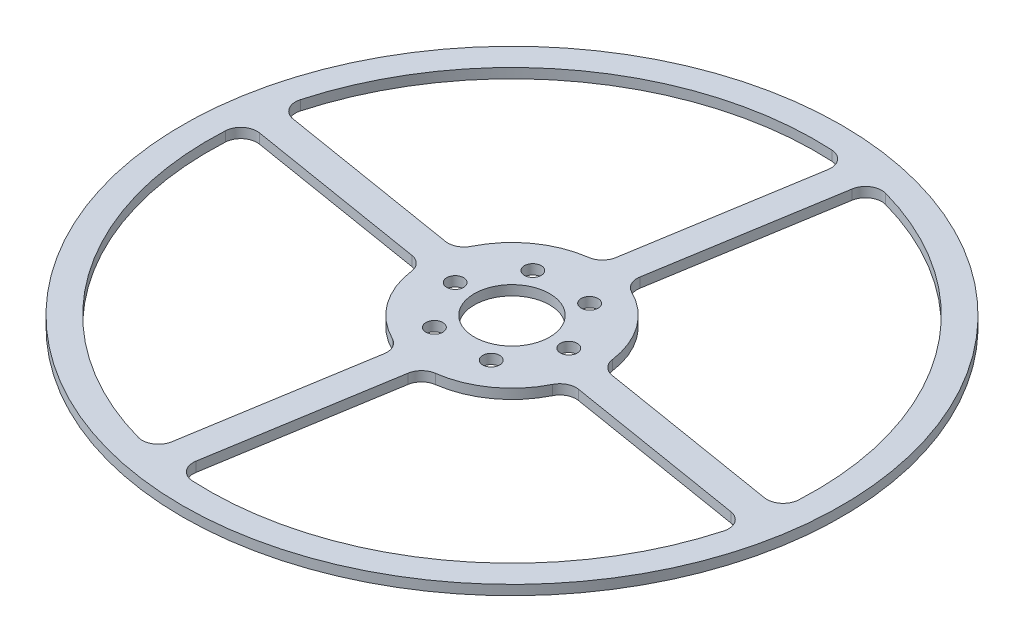
SolidWorks part; units mm, degrees
ref_plane "Front Plane" through (0, 0, 0) normal (0, 0, 1) x (1, 0, 0)
ref_plane "Top Plane" through (0, 0, 0) normal (0, 1, 0) x (1, 0, 0)
ref_plane "Right Plane" through (0, 0, 0) normal (1, 0, 0) x (0, 0, -1)
ref_axis "Axis1" through (0, -0.15, 0) along (0, 1, 0)
sketch "Sketch1" plane through (0, 0, 0) normal (0, 1, 0) x (1, 0, 0)
  line L1 (17.5, 0) -> (8.75, 15.1554) construction
  line L2 (8.75, 15.1554) -> (-8.75, 15.1554) construction
  line L3 (-8.75, 15.1554) -> (-17.5, 0) construction
  line L4 (-17.5, 0) -> (-8.75, -15.1554) construction
  line L5 (-8.75, -15.1554) -> (8.75, -15.1554) construction
  line L6 (8.75, -15.1554) -> (17.5, 0) construction
  circle A0 centre (0, 0) radius 15.1554 construction
  circle A1 centre (8.75, 15.1554) radius 2.6
  circle A2 centre (17.5, 0) radius 2.6
  circle A3 centre (8.75, -15.1554) radius 2.6
  circle A4 centre (-8.75, -15.1554) radius 2.6
  circle A5 centre (-17.5, 0) radius 2.6
  circle A6 centre (-8.75, 15.1554) radius 2.6
  circle A7 centre (0, 0) radius 11.6
  circle A8 centre (0, 0) radius 101.6 construction
  dimension "D1" = 5.2
  dimension "D2" = 23.2
  dimension "D3" = 203.2
  dimension "D4" = 35
sketch "Sketch2" plane through (0, 0, 0) normal (0, 1, 0) x (1, 0, 0)
  line L0 (0, -1000) -> (0, 49000) construction
  line L1 (2.0865, 101.5786) -> (-2.0865, 108.8065) construction
  line L2 (35.7602, 94.9919) -> (0, 0) construction
  line L3 (-2.0865, 108.8065) -> (35.4897, 95.0942) construction
  line L4 (-1000, 0) -> (49000, 0) construction
  line L5 (16.7016, 101.9503) -> (0, 0) construction
  line L6 (9.7839, 87.5587) -> (0.5839, 31.3992)
  line L7 (18.6656, 86.1037) -> (9.4655, 29.9442)
  line L8 (5.1839, 59.4789) -> (14.0655, 58.0239) construction
  line L9 (0, 0) -> (-92.2701, 15.1157) construction
  line L10 (-86.1037, 18.6656) -> (-29.9442, 9.4655)
  line L11 (-87.5587, 9.7839) -> (-31.3992, 0.5839)
  line L12 (-58.0239, 14.0655) -> (-59.4789, 5.1839) construction
  circle A0 centre (0, 0) radius 101.6 construction
  arc A1 (2.0865, 101.5786) -> (35.4897, 95.0942) centre (0.0357, 1.7368) cw construction
  arc A2 (35.4897, 95.0942) -> (35.7602, 94.9919) centre (70.9437, 188.4515) ccw construction
  circle A3 centre (0, 0) radius 101.5 construction
  arc A4 (-2.0865, 108.8065) -> (-6.1154, 101.3156) centre (-6.4167, 106.3065) cw construction
  circle A5 centre (0, 0) radius 27.5 construction
  circle A6 centre (0, 0) radius 93.5 construction
  arc A7 (9.4655, 29.9442) -> (12.1844, 24.6534) centre (14.3997, 29.1359) ccw
  arc A8 (18.6656, 86.1037) -> (24.9331, 90.1143) centre (23.5998, 85.2954) cw
  arc A9 (0.5839, 31.3992) -> (-3.6811, 27.2525) centre (-4.3504, 32.2075) cw
  arc A10 (9.7839, 87.5587) -> (5.1237, 93.3595) centre (4.8497, 88.367) ccw
  arc A11 (-6.1154, 101.3156) -> (35.7602, 94.9919) centre (0, 0) ccw
  arc A12 (-29.9442, 9.4655) -> (-24.6534, 12.1844) centre (-29.1359, 14.3997) ccw
  arc A13 (-31.3992, 0.5839) -> (-27.2525, -3.6811) centre (-32.2075, -4.3504) cw
  arc A14 (-87.5587, 9.7839) -> (-93.3595, 5.1237) centre (-88.367, 4.8497) ccw
  arc A15 (-86.1037, 18.6656) -> (-90.1143, 24.9331) centre (-85.2954, 23.5998) cw
  arc A16 (5.1237, 93.3595) -> (-90.1143, 24.9331) centre (0, 0) ccw
  arc A17 (-93.3595, 5.1237) -> (24.9331, 90.1143) centre (0, 0) ccw
  arc A18 (-3.6811, 27.2525) -> (-24.6534, 12.1844) centre (0, 0) ccw
  arc A19 (12.1844, 24.6534) -> (-27.2525, -3.6811) centre (0, 0) cw
  arc A20 (-6.1154, 101.3156) -> (35.7602, 94.9919) centre (0, 0) cw
  point P7 (0, 105.1925)
  point P16 (-101.5, 0)
  point P17 (-101.6, 0)
  point P21 (27.5, 0)
  point P25 (-93.5, 0)
  point P34 (9.6247, 58.7514)
  point P49 (-58.7514, 9.6247)
  dimension "D3" = 5
  dimension "D8" = 5
  dimension "D1" = 30
  dimension "D2" = 0.1
  dimension "D4" = 40
  dimension "D5" = 10
  dimension "D6" = 8
  dimension "D7" = 9
  dimension "D9" = 9
extrude "Boss-Extrude1" add sketch "Sketch2" along normal blind 3.02
pattern_circular "CirPattern1" count 2 over 360 about axis through (0, -0.15, 0) along (0, 1, 0) of bodies 101
combine bodies "Combine1" bodies to combine 101 102
extrude "Cut-Extrude2" cut sketch "Sketch1" along normal through all
